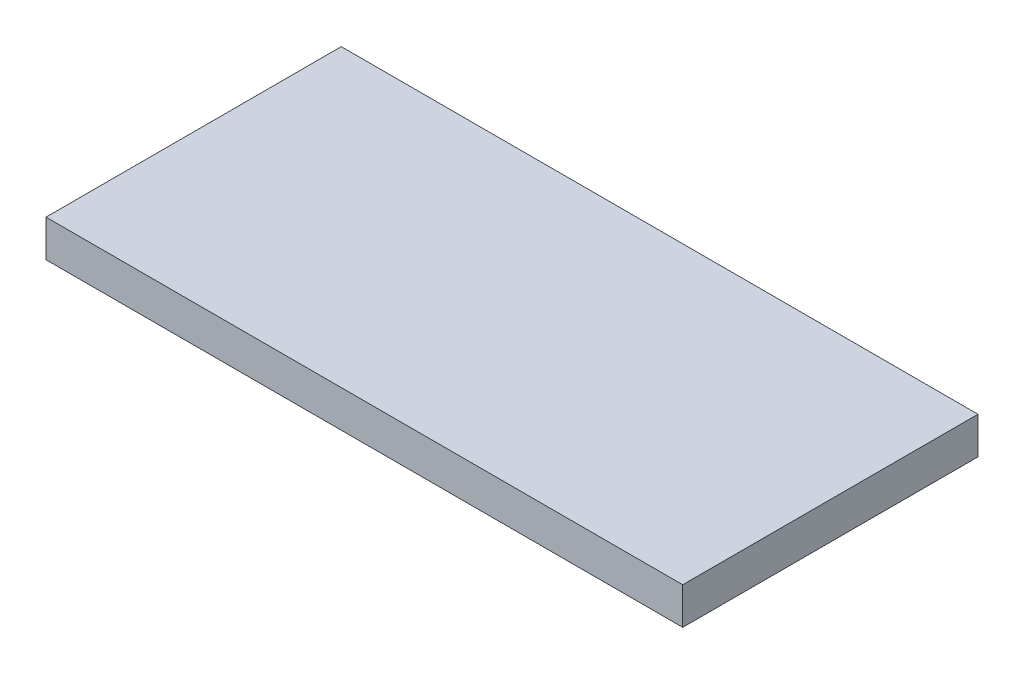
SolidWorks part; units mm, degrees
ref_plane "Front Plane" through (0, 0, 0) normal (0, 0, 1) x (1, 0, 0)
ref_plane "Top Plane" through (0, 0, 0) normal (0, 1, 0) x (1, 0, 0)
ref_plane "Right Plane" through (0, 0, 0) normal (1, 0, 0) x (0, 0, -1)
sketch "Sketch1" plane through (0, 0, 0) normal (0, 0, 1) x (1, 0, 0)
  line L0 (-430.4163, 0) -> (430.4163, 0) construction
  line L1 (0, -313.8614) -> (0, 313.8614) construction
  line L3 (-438.15, -25.4) -> (438.15, -25.4)
  line L4 (-438.15, -25.4) -> (-438.15, 25.4)
  line L5 (-438.15, 25.4) -> (438.15, 25.4)
  line L6 (438.15, -25.4) -> (438.15, 25.4)
  line L7 (-438.15, -25.4) -> (438.15, 25.4) construction
  line L8 (-438.15, 25.4) -> (438.15, -25.4) construction
  point P0 (0, 0)
  point P4 (0, 0)
  point P8 (0, 0)
  dimension "D1" = 876.3
  dimension "D2" = 50.8
extrude "Boss-Extrude1" add sketch "Sketch1" along normal mid plane 406.4
